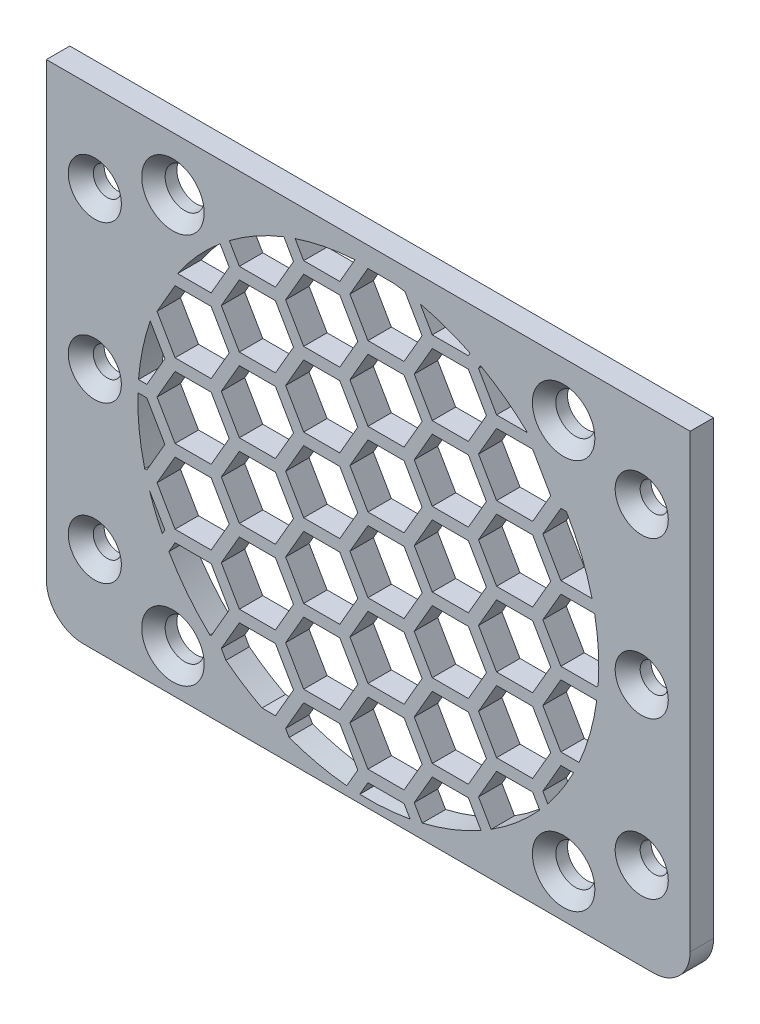
SolidWorks part; units mm, degrees
ref_plane "Front Plane" through (0, 0, 0) normal (0, 0, 1) x (1, 0, 0)
ref_plane "Top Plane" through (0, 0, 0) normal (0, 1, 0) x (1, 0, 0)
ref_plane "Right Plane" through (0, 0, 0) normal (1, 0, 0) x (0, 0, -1)
sketch "Sketch1" plane through (0, 0, 0) normal (0, 0, 1) x (1, 0, 0)
  line L1 (0, 0) -> (11, 0)
  line L2 (0, 0) -> (0, 63)
  line L3 (0, 63) -> (11, 63)
  line L4 (11, 0) -> (11, 63)
  line L5 (0, 0) -> (-61, 0)
  line L6 (0, 0) -> (0, 63)
  line L7 (0, 63) -> (-61, 63)
  line L8 (-61, 0) -> (-61, 63)
  line L9 (-61, 0) -> (-72, 0)
  line L10 (-61, 0) -> (-61, 63)
  line L11 (-61, 63) -> (-72, 63)
  line L12 (-72, 0) -> (-72, 63)
  line L13 (0, 0) -> (-60, 0)
  line L14 (0, 0) -> (0, 60)
  line L15 (0, 60) -> (-60, 60)
  line L16 (-60, 0) -> (-60, 60)
  dimension "D1" = 63
  dimension "D2" = 11
  dimension "D3" = 11
  dimension "D4" = 60
  dimension "D5" = 60
  dimension "D6" = 1
extrude "Boss-Extrude1" add sketch "Sketch1" along normal blind 3 contours L12 L9 L8 L11 | L5 L16 L15 L6 L7 L8 | L16 L5 L2 L15 | L1 L4 L3 L6 L2 region at (5.5, 31.5, 0) region at (-30, 30, 0) region at (-30, 60.8769, 0) region at (-66.5, 31.5, 0)
hole_wizard "CSK for M3 Flat Head Machine Screw1" positions "Sketch2" profile "Sketch3" countersink size "M3" standard "ANSI Metric"
sketch "Sketch2" plane through (0, 0, 3) normal (0, 0, 1) x (1, 0, 0)
  line L0 (-72, 0) -> (-72, 63) construction
  line L1 (11, 0) -> (11, 63) construction
  line L2 (-72, 0) -> (-72, 63) construction
  point P0 (-65.5, 31.5)
  point P2 (-65.5, 51.5)
  point P4 (-65.5, 11.5)
  point P6 (4.5, 11.5)
  point P8 (4.5, 31.5)
  point P10 (4.5, 51.5)
  point P37 (-72, 31.5)
  dimension "D1" = 6.5
  dimension "D2" = 6.5
  dimension "D3" = 20
  dimension "D4" = 20
  dimension "D5" = 20
  dimension "D6" = 20
sketch "Sketch3" plane through (-65.5, 31.5, 3) normal (1, 0, 0) x (0, -1, 0)
  line L0 (0, 0) -> (0, 7.0815)
  line L1 (0, 7.0815) -> (1.8, 6)
  line L2 (1.8, 6) -> (1.8, 1.6)
  line L3 (1.8, 1.6) -> (3.4, 0)
  line L5 (3.4, 0) -> (0, 0)
  line L6 (-1.8, 1.6) -> (-3.4, 0) construction
  line L10 (0, 7.0815) -> (-1.8, 6) construction
  line L11 (0, -6.35) -> (0, 107.95) construction
  dimension "Hole Dia." = 3.6
  dimension "Hole Depth" = 6
  dimension "Near C'Sink Dia." = 6.8
  dimension "Near C'Sink Angle" = 90
  dimension "Drill Angle" = 118
fillet "Fillet1" radius 5 2 edges at (-72, 0, 1.5) (11, 0, 1.5)
sketch "Sketch4" plane through (0, 0, 3) normal (0, 0, 1) x (1, 0, 0)
  line L0 (11, 5) -> (11, 63) construction
  line L1 (6, 0) -> (-67, 0) construction
  line L2 (-72, 5) -> (-72, 63) construction
  line L3 (11, 63) -> (-72, 63) construction
  line L4 (11, 5) -> (11, 63)
  line L5 (6, 0) -> (-67, 0)
  line L6 (-72, 5) -> (-72, 63)
  line L7 (11, 63) -> (-72, 63)
  line L8 (10.7, 5) -> (10.7, 62.7)
  line L9 (10.7, 62.7) -> (-71.7, 62.7)
  line L10 (-71.7, 5) -> (-71.7, 62.7)
  line L11 (6, 0.3) -> (-67, 0.3)
  arc A0 (6, 0) -> (11, 5) centre (6, 5) ccw construction
  arc A1 (-72, 5) -> (-67, 0) centre (-67, 5) ccw construction
  arc A2 (6, 0) -> (11, 5) centre (6, 5) ccw
  arc A3 (-72, 5) -> (-67, 0) centre (-67, 5) ccw
  arc A4 (-71.7, 5) -> (-67, 0.3) centre (-67, 5) ccw
  arc A5 (6, 0.3) -> (10.7, 5) centre (6, 5) ccw
  dimension "D1" = 0.3
extrude "Cut-Extrude1" cut sketch "Sketch4" against normal through all
sketch "Sketch5" plane through (0, 0, 3) normal (0, 0, 1) x (1, 0, 0)
  line L0 (-67, 0.3) -> (6, 0.3) construction
  line L1 (-60.5, 60.8) -> (-0.5, 60.8)
  line L2 (-60.5, 60.8) -> (-60.5, 0.8)
  line L3 (-60.5, 0.8) -> (-0.5, 0.8)
  line L4 (-0.5, 60.8) -> (-0.5, 0.8)
  line L5 (-60.5, 60.8) -> (-0.5, 0.8) construction
  line L6 (-60.5, 0.8) -> (-0.5, 60.8) construction
  line L7 (-55.5, 55.8) -> (-5.5, 55.8)
  line L8 (-55.5, 55.8) -> (-55.5, 5.8)
  line L9 (-55.5, 5.8) -> (-5.5, 5.8)
  line L10 (-5.5, 55.8) -> (-5.5, 5.8)
  line L11 (-55.5, 55.8) -> (-5.5, 5.8) construction
  line L12 (-55.5, 5.8) -> (-5.5, 55.8) construction
  point P0 (-30.5, 30.8)
  point P5 (-30.5, 30.8)
  point P16 (-30.5, 0.3)
  dimension "D1" = 50
  dimension "D2" = 60
  dimension "D3" = 0.5
sketch "Sketch6" plane through (0, 0, 3) normal (0, 0, 1) x (1, 0, 0)
  point P0 (-55.5, 55.8)
  point P3 (-5.5, 55.8)
  point P6 (-5.5, 5.8)
  point P9 (-55.5, 5.8)
hole_wizard "CSK for M4 Flat Head Machine Screw1" positions "Sketch6" profile "Sketch7" countersink size "M4" standard "ANSI Metric"
sketch "Sketch7" plane through (-55.5, 55.8, 3) normal (1, 0, 0) x (0, -1, 0)
  line L0 (0, 0) -> (0, 8.5022)
  line L1 (0, 8.5022) -> (2.5, 7)
  line L2 (2.5, 7) -> (2.5, 1.5)
  line L3 (2.5, 1.5) -> (4, 0)
  line L5 (4, 0) -> (0, 0)
  line L6 (-2.5, 1.5) -> (-4, 0) construction
  line L10 (0, 8.5022) -> (-2.5, 7) construction
  line L11 (0, -6.35) -> (0, 107.95) construction
  dimension "Hole Dia." = 5
  dimension "Hole Depth" = 7
  dimension "Near C'Sink Dia." = 8
  dimension "Near C'Sink Angle" = 90
  dimension "Drill Angle" = 118
sketch "Sketch8" plane through (0, 0, 3) normal (0, 0, 1) x (1, 0, 0)
  circle A0 centre (-30.5, 30.8) radius 29.5
  dimension "D1" = 59
extrude "Cut-Extrude2" cut sketch "Sketch8" against normal through all
sketch "Sketch9" plane through (0, 0, 3) normal (0, 0, 1) x (1, 0, 0)
  line L0 (-36.46, 32.375) -> (-28.2328, 37.125) construction
  line L1 (-31.8412, 32.375) -> (-34.1506, 36.375)
  line L2 (-34.1506, 36.375) -> (-38.7694, 36.375)
  line L3 (-38.7694, 36.375) -> (-41.0788, 32.375)
  line L4 (-41.0788, 32.375) -> (-38.7694, 28.375)
  line L5 (-38.7694, 28.375) -> (-34.1506, 28.375)
  line L6 (-34.1506, 28.375) -> (-31.8412, 32.375)
  line L7 (-23.614, 37.125) -> (-25.9234, 41.125)
  line L8 (-25.9234, 41.125) -> (-30.5422, 41.125)
  line L9 (-30.5422, 41.125) -> (-32.8516, 37.125)
  line L10 (-32.8516, 37.125) -> (-30.5422, 33.125)
  line L11 (-30.5422, 33.125) -> (-25.9234, 33.125)
  line L12 (-25.9234, 33.125) -> (-23.614, 37.125)
  line L13 (-36.46, 32.375) -> (-28.2328, 32.375) construction
  line L14 (-31.8412, 22.875) -> (-34.1506, 26.875)
  line L15 (-34.1506, 26.875) -> (-38.7694, 26.875)
  line L16 (-38.7694, 26.875) -> (-41.0788, 22.875)
  line L17 (-41.0788, 22.875) -> (-38.7694, 18.875)
  line L18 (-38.7694, 18.875) -> (-34.1506, 18.875)
  line L19 (-34.1506, 18.875) -> (-31.8412, 22.875)
  line L20 (-23.614, 27.625) -> (-25.9234, 31.625)
  line L21 (-25.9234, 31.625) -> (-30.5422, 31.625)
  line L22 (-30.5422, 31.625) -> (-32.8516, 27.625)
  line L23 (-32.8516, 27.625) -> (-30.5422, 23.625)
  line L24 (-30.5422, 23.625) -> (-25.9234, 23.625)
  line L25 (-25.9234, 23.625) -> (-23.614, 27.625)
  line L26 (-15.3812, 32.375) -> (-17.6906, 36.375)
  line L27 (-17.6906, 36.375) -> (-22.3094, 36.375)
  line L28 (-22.3094, 36.375) -> (-24.6188, 32.375)
  line L29 (-24.6188, 32.375) -> (-22.3094, 28.375)
  line L30 (-22.3094, 28.375) -> (-17.6906, 28.375)
  line L31 (-17.6906, 28.375) -> (-15.3812, 32.375)
  line L32 (1.0788, 32.375) -> (-1.2306, 36.375)
  line L33 (-1.2306, 36.375) -> (-5.8494, 36.375)
  line L34 (-5.8494, 36.375) -> (-8.1588, 32.375)
  line L35 (-8.1588, 32.375) -> (-5.8494, 28.375)
  line L36 (-5.8494, 28.375) -> (-1.2306, 28.375)
  line L37 (-1.2306, 28.375) -> (1.0788, 32.375)
  line L38 (-15.3812, 22.875) -> (-17.6906, 26.875)
  line L39 (-17.6906, 26.875) -> (-22.3094, 26.875)
  line L40 (-22.3094, 26.875) -> (-24.6188, 22.875)
  line L41 (-24.6188, 22.875) -> (-22.3094, 18.875)
  line L42 (-22.3094, 18.875) -> (-17.6906, 18.875)
  line L43 (-17.6906, 18.875) -> (-15.3812, 22.875)
  line L44 (1.0788, 22.875) -> (-1.2306, 26.875)
  line L45 (-1.2306, 26.875) -> (-5.8494, 26.875)
  line L46 (-5.8494, 26.875) -> (-8.1588, 22.875)
  line L47 (-8.1588, 22.875) -> (-5.8494, 18.875)
  line L48 (-5.8494, 18.875) -> (-1.2306, 18.875)
  line L49 (-1.2306, 18.875) -> (1.0788, 22.875)
  line L50 (-15.3812, 13.375) -> (-17.6906, 17.375)
  line L51 (-17.6906, 17.375) -> (-22.3094, 17.375)
  line L52 (-22.3094, 17.375) -> (-24.6188, 13.375)
  line L53 (-24.6188, 13.375) -> (-22.3094, 9.375)
  line L54 (-22.3094, 9.375) -> (-17.6906, 9.375)
  line L55 (-17.6906, 9.375) -> (-15.3812, 13.375)
  line L56 (1.0788, 13.375) -> (-1.2306, 17.375)
  line L57 (-1.2306, 17.375) -> (-5.8494, 17.375)
  line L58 (-5.8494, 17.375) -> (-8.1588, 13.375)
  line L59 (-8.1588, 13.375) -> (-5.8494, 9.375)
  line L60 (-5.8494, 9.375) -> (-1.2306, 9.375)
  line L61 (-1.2306, 9.375) -> (1.0788, 13.375)
  line L62 (-15.3812, 3.875) -> (-17.6906, 7.875)
  line L63 (-17.6906, 7.875) -> (-22.3094, 7.875)
  line L64 (-22.3094, 7.875) -> (-24.6188, 3.875)
  line L65 (-24.6188, 3.875) -> (-22.3094, -0.125)
  line L66 (-22.3094, -0.125) -> (-17.6906, -0.125)
  line L67 (-17.6906, -0.125) -> (-15.3812, 3.875)
  line L68 (1.0788, 3.875) -> (-1.2306, 7.875)
  line L69 (-1.2306, 7.875) -> (-5.8494, 7.875)
  line L70 (-5.8494, 7.875) -> (-8.1588, 3.875)
  line L71 (-8.1588, 3.875) -> (-5.8494, -0.125)
  line L72 (-5.8494, -0.125) -> (-1.2306, -0.125)
  line L73 (-1.2306, -0.125) -> (1.0788, 3.875)
  line L74 (-31.8412, 22.875) -> (-34.1506, 26.875)
  line L75 (-34.1506, 26.875) -> (-38.7694, 26.875)
  line L76 (-38.7694, 26.875) -> (-41.0788, 22.875)
  line L77 (-41.0788, 22.875) -> (-38.7694, 18.875)
  line L78 (-38.7694, 18.875) -> (-34.1506, 18.875)
  line L79 (-34.1506, 18.875) -> (-31.8412, 22.875)
  line L80 (-31.8412, 13.375) -> (-34.1506, 17.375)
  line L81 (-34.1506, 17.375) -> (-38.7694, 17.375)
  line L82 (-38.7694, 17.375) -> (-41.0788, 13.375)
  line L83 (-41.0788, 13.375) -> (-38.7694, 9.375)
  line L84 (-38.7694, 9.375) -> (-34.1506, 9.375)
  line L85 (-34.1506, 9.375) -> (-31.8412, 13.375)
  line L86 (-31.8412, 3.875) -> (-34.1506, 7.875)
  line L87 (-34.1506, 7.875) -> (-38.7694, 7.875)
  line L88 (-38.7694, 7.875) -> (-41.0788, 3.875)
  line L89 (-41.0788, 3.875) -> (-38.7694, -0.125)
  line L90 (-38.7694, -0.125) -> (-34.1506, -0.125)
  line L91 (-34.1506, -0.125) -> (-31.8412, 3.875)
  line L92 (-31.8412, 41.875) -> (-34.1506, 45.875)
  line L93 (-34.1506, 45.875) -> (-38.7694, 45.875)
  line L94 (-38.7694, 45.875) -> (-41.0788, 41.875)
  line L95 (-41.0788, 41.875) -> (-38.7694, 37.875)
  line L96 (-38.7694, 37.875) -> (-34.1506, 37.875)
  line L97 (-34.1506, 37.875) -> (-31.8412, 41.875)
  line L98 (-15.3812, 41.875) -> (-17.6906, 45.875)
  line L99 (-17.6906, 45.875) -> (-22.3094, 45.875)
  line L100 (-22.3094, 45.875) -> (-24.6188, 41.875)
  line L101 (-24.6188, 41.875) -> (-22.3094, 37.875)
  line L102 (-22.3094, 37.875) -> (-17.6906, 37.875)
  line L103 (-17.6906, 37.875) -> (-15.3812, 41.875)
  line L104 (1.0788, 41.875) -> (-1.2306, 45.875)
  line L105 (-1.2306, 45.875) -> (-5.8494, 45.875)
  line L106 (-5.8494, 45.875) -> (-8.1588, 41.875)
  line L107 (-8.1588, 41.875) -> (-5.8494, 37.875)
  line L108 (-5.8494, 37.875) -> (-1.2306, 37.875)
  line L109 (-1.2306, 37.875) -> (1.0788, 41.875)
  line L110 (-31.8412, 51.375) -> (-34.1506, 55.375)
  line L111 (-34.1506, 55.375) -> (-38.7694, 55.375)
  line L112 (-38.7694, 55.375) -> (-41.0788, 51.375)
  line L113 (-41.0788, 51.375) -> (-38.7694, 47.375)
  line L114 (-38.7694, 47.375) -> (-34.1506, 47.375)
  line L115 (-34.1506, 47.375) -> (-31.8412, 51.375)
  line L116 (-15.3812, 51.375) -> (-17.6906, 55.375)
  line L117 (-17.6906, 55.375) -> (-22.3094, 55.375)
  line L118 (-22.3094, 55.375) -> (-24.6188, 51.375)
  line L119 (-24.6188, 51.375) -> (-22.3094, 47.375)
  line L120 (-22.3094, 47.375) -> (-17.6906, 47.375)
  line L121 (-17.6906, 47.375) -> (-15.3812, 51.375)
  line L122 (1.0788, 51.375) -> (-1.2306, 55.375)
  line L123 (-1.2306, 55.375) -> (-5.8494, 55.375)
  line L124 (-5.8494, 55.375) -> (-8.1588, 51.375)
  line L125 (-8.1588, 51.375) -> (-5.8494, 47.375)
  line L126 (-5.8494, 47.375) -> (-1.2306, 47.375)
  line L127 (-1.2306, 47.375) -> (1.0788, 51.375)
  line L128 (-31.8412, 60.875) -> (-34.1506, 64.875)
  line L129 (-34.1506, 64.875) -> (-38.7694, 64.875)
  line L130 (-38.7694, 64.875) -> (-41.0788, 60.875)
  line L131 (-41.0788, 60.875) -> (-38.7694, 56.875)
  line L132 (-38.7694, 56.875) -> (-34.1506, 56.875)
  line L133 (-34.1506, 56.875) -> (-31.8412, 60.875)
  line L134 (-15.3812, 60.875) -> (-17.6906, 64.875)
  line L135 (-17.6906, 64.875) -> (-22.3094, 64.875)
  line L136 (-22.3094, 64.875) -> (-24.6188, 60.875)
  line L137 (-24.6188, 60.875) -> (-22.3094, 56.875)
  line L138 (-22.3094, 56.875) -> (-17.6906, 56.875)
  line L139 (-17.6906, 56.875) -> (-15.3812, 60.875)
  line L140 (1.0788, 60.875) -> (-1.2306, 64.875)
  line L141 (-1.2306, 64.875) -> (-5.8494, 64.875)
  line L142 (-5.8494, 64.875) -> (-8.1588, 60.875)
  line L143 (-8.1588, 60.875) -> (-5.8494, 56.875)
  line L144 (-5.8494, 56.875) -> (-1.2306, 56.875)
  line L145 (-1.2306, 56.875) -> (1.0788, 60.875)
  line L146 (-23.614, 46.625) -> (-25.9234, 50.625)
  line L147 (-25.9234, 50.625) -> (-30.5422, 50.625)
  line L148 (-30.5422, 50.625) -> (-32.8516, 46.625)
  line L149 (-32.8516, 46.625) -> (-30.5422, 42.625)
  line L150 (-30.5422, 42.625) -> (-25.9234, 42.625)
  line L151 (-25.9234, 42.625) -> (-23.614, 46.625)
  line L152 (-23.614, 56.125) -> (-25.9234, 60.125)
  line L153 (-25.9234, 60.125) -> (-30.5422, 60.125)
  line L154 (-30.5422, 60.125) -> (-32.8516, 56.125)
  line L155 (-32.8516, 56.125) -> (-30.5422, 52.125)
  line L156 (-30.5422, 52.125) -> (-25.9234, 52.125)
  line L157 (-25.9234, 52.125) -> (-23.614, 56.125)
  line L158 (-23.614, 18.125) -> (-25.9234, 22.125)
  line L159 (-25.9234, 22.125) -> (-30.5422, 22.125)
  line L160 (-30.5422, 22.125) -> (-32.8516, 18.125)
  line L161 (-32.8516, 18.125) -> (-30.5422, 14.125)
  line L162 (-30.5422, 14.125) -> (-25.9234, 14.125)
  line L163 (-25.9234, 14.125) -> (-23.614, 18.125)
  line L164 (-23.614, 8.625) -> (-25.9234, 12.625)
  line L165 (-25.9234, 12.625) -> (-30.5422, 12.625)
  line L166 (-30.5422, 12.625) -> (-32.8516, 8.625)
  line L167 (-32.8516, 8.625) -> (-30.5422, 4.625)
  line L168 (-30.5422, 4.625) -> (-25.9234, 4.625)
  line L169 (-25.9234, 4.625) -> (-23.614, 8.625)
  line L170 (-23.614, -0.875) -> (-25.9234, 3.125)
  line L171 (-25.9234, 3.125) -> (-30.5422, 3.125)
  line L172 (-30.5422, 3.125) -> (-32.8516, -0.875)
  line L173 (-32.8516, -0.875) -> (-30.5422, -4.875)
  line L174 (-30.5422, -4.875) -> (-25.9234, -4.875)
  line L175 (-25.9234, -4.875) -> (-23.614, -0.875)
  line L176 (-7.154, 56.125) -> (-9.4634, 60.125)
  line L177 (-9.4634, 60.125) -> (-14.0822, 60.125)
  line L178 (-14.0822, 60.125) -> (-16.3916, 56.125)
  line L179 (-16.3916, 56.125) -> (-14.0822, 52.125)
  line L180 (-14.0822, 52.125) -> (-9.4634, 52.125)
  line L181 (-9.4634, 52.125) -> (-7.154, 56.125)
  line L182 (-7.154, 46.625) -> (-9.4634, 50.625)
  line L183 (-9.4634, 50.625) -> (-14.0822, 50.625)
  line L184 (-14.0822, 50.625) -> (-16.3916, 46.625)
  line L185 (-16.3916, 46.625) -> (-14.0822, 42.625)
  line L186 (-14.0822, 42.625) -> (-9.4634, 42.625)
  line L187 (-9.4634, 42.625) -> (-7.154, 46.625)
  line L188 (-7.154, 37.125) -> (-9.4634, 41.125)
  line L189 (-9.4634, 41.125) -> (-14.0822, 41.125)
  line L190 (-14.0822, 41.125) -> (-16.3916, 37.125)
  line L191 (-16.3916, 37.125) -> (-14.0822, 33.125)
  line L192 (-14.0822, 33.125) -> (-9.4634, 33.125)
  line L193 (-9.4634, 33.125) -> (-7.154, 37.125)
  line L194 (-7.154, 27.625) -> (-9.4634, 31.625)
  line L195 (-9.4634, 31.625) -> (-14.0822, 31.625)
  line L196 (-14.0822, 31.625) -> (-16.3916, 27.625)
  line L197 (-16.3916, 27.625) -> (-14.0822, 23.625)
  line L198 (-14.0822, 23.625) -> (-9.4634, 23.625)
  line L199 (-9.4634, 23.625) -> (-7.154, 27.625)
  line L200 (-7.154, 18.125) -> (-9.4634, 22.125)
  line L201 (-9.4634, 22.125) -> (-14.0822, 22.125)
  line L202 (-14.0822, 22.125) -> (-16.3916, 18.125)
  line L203 (-16.3916, 18.125) -> (-14.0822, 14.125)
  line L204 (-14.0822, 14.125) -> (-9.4634, 14.125)
  line L205 (-9.4634, 14.125) -> (-7.154, 18.125)
  line L206 (-7.154, 8.625) -> (-9.4634, 12.625)
  line L207 (-9.4634, 12.625) -> (-14.0822, 12.625)
  line L208 (-14.0822, 12.625) -> (-16.3916, 8.625)
  line L209 (-16.3916, 8.625) -> (-14.0822, 4.625)
  line L210 (-14.0822, 4.625) -> (-9.4634, 4.625)
  line L211 (-9.4634, 4.625) -> (-7.154, 8.625)
  line L212 (-48.3012, 60.875) -> (-50.6106, 64.875)
  line L213 (-50.6106, 64.875) -> (-55.2294, 64.875)
  line L214 (-55.2294, 64.875) -> (-57.5388, 60.875)
  line L215 (-57.5388, 60.875) -> (-55.2294, 56.875)
  line L216 (-55.2294, 56.875) -> (-50.6106, 56.875)
  line L217 (-50.6106, 56.875) -> (-48.3012, 60.875)
  line L218 (-48.3012, 51.375) -> (-50.6106, 55.375)
  line L219 (-50.6106, 55.375) -> (-55.2294, 55.375)
  line L220 (-55.2294, 55.375) -> (-57.5388, 51.375)
  line L221 (-57.5388, 51.375) -> (-55.2294, 47.375)
  line L222 (-55.2294, 47.375) -> (-50.6106, 47.375)
  line L223 (-50.6106, 47.375) -> (-48.3012, 51.375)
  line L224 (-40.074, 56.125) -> (-42.3834, 60.125)
  line L225 (-42.3834, 60.125) -> (-47.0022, 60.125)
  line L226 (-47.0022, 60.125) -> (-49.3116, 56.125)
  line L227 (-49.3116, 56.125) -> (-47.0022, 52.125)
  line L228 (-47.0022, 52.125) -> (-42.3834, 52.125)
  line L229 (-42.3834, 52.125) -> (-40.074, 56.125)
  line L230 (-40.074, 46.625) -> (-42.3834, 50.625)
  line L231 (-42.3834, 50.625) -> (-47.0022, 50.625)
  line L232 (-47.0022, 50.625) -> (-49.3116, 46.625)
  line L233 (-49.3116, 46.625) -> (-47.0022, 42.625)
  line L234 (-47.0022, 42.625) -> (-42.3834, 42.625)
  line L235 (-42.3834, 42.625) -> (-40.074, 46.625)
  line L236 (-48.3012, 41.875) -> (-50.6106, 45.875)
  line L237 (-50.6106, 45.875) -> (-55.2294, 45.875)
  line L238 (-55.2294, 45.875) -> (-57.5388, 41.875)
  line L239 (-57.5388, 41.875) -> (-55.2294, 37.875)
  line L240 (-55.2294, 37.875) -> (-50.6106, 37.875)
  line L241 (-50.6106, 37.875) -> (-48.3012, 41.875)
  line L242 (-40.074, 37.125) -> (-42.3834, 41.125)
  line L243 (-42.3834, 41.125) -> (-47.0022, 41.125)
  line L244 (-47.0022, 41.125) -> (-49.3116, 37.125)
  line L245 (-49.3116, 37.125) -> (-47.0022, 33.125)
  line L246 (-47.0022, 33.125) -> (-42.3834, 33.125)
  line L247 (-42.3834, 33.125) -> (-40.074, 37.125)
  line L248 (-48.3012, 32.375) -> (-50.6106, 36.375)
  line L249 (-50.6106, 36.375) -> (-55.2294, 36.375)
  line L250 (-55.2294, 36.375) -> (-57.5388, 32.375)
  line L251 (-57.5388, 32.375) -> (-55.2294, 28.375)
  line L252 (-55.2294, 28.375) -> (-50.6106, 28.375)
  line L253 (-50.6106, 28.375) -> (-48.3012, 32.375)
  line L254 (-40.074, 27.625) -> (-42.3834, 31.625)
  line L255 (-42.3834, 31.625) -> (-47.0022, 31.625)
  line L256 (-47.0022, 31.625) -> (-49.3116, 27.625)
  line L257 (-49.3116, 27.625) -> (-47.0022, 23.625)
  line L258 (-47.0022, 23.625) -> (-42.3834, 23.625)
  line L259 (-42.3834, 23.625) -> (-40.074, 27.625)
  line L260 (-48.3012, 22.875) -> (-50.6106, 26.875)
  line L261 (-50.6106, 26.875) -> (-55.2294, 26.875)
  line L262 (-55.2294, 26.875) -> (-57.5388, 22.875)
  line L263 (-57.5388, 22.875) -> (-55.2294, 18.875)
  line L264 (-55.2294, 18.875) -> (-50.6106, 18.875)
  line L265 (-50.6106, 18.875) -> (-48.3012, 22.875)
  line L266 (-40.074, 18.125) -> (-42.3834, 22.125)
  line L267 (-42.3834, 22.125) -> (-47.0022, 22.125)
  line L268 (-47.0022, 22.125) -> (-49.3116, 18.125)
  line L269 (-49.3116, 18.125) -> (-47.0022, 14.125)
  line L270 (-47.0022, 14.125) -> (-42.3834, 14.125)
  line L271 (-42.3834, 14.125) -> (-40.074, 18.125)
  line L272 (-48.3012, 13.375) -> (-50.6106, 17.375)
  line L273 (-50.6106, 17.375) -> (-55.2294, 17.375)
  line L274 (-55.2294, 17.375) -> (-57.5388, 13.375)
  line L275 (-57.5388, 13.375) -> (-55.2294, 9.375)
  line L276 (-55.2294, 9.375) -> (-50.6106, 9.375)
  line L277 (-50.6106, 9.375) -> (-48.3012, 13.375)
  line L278 (-40.074, 8.625) -> (-42.3834, 12.625)
  line L279 (-42.3834, 12.625) -> (-47.0022, 12.625)
  line L280 (-47.0022, 12.625) -> (-49.3116, 8.625)
  line L281 (-49.3116, 8.625) -> (-47.0022, 4.625)
  line L282 (-47.0022, 4.625) -> (-42.3834, 4.625)
  line L283 (-42.3834, 4.625) -> (-40.074, 8.625)
  line L284 (-48.3012, 3.875) -> (-50.6106, 7.875)
  line L285 (-50.6106, 7.875) -> (-55.2294, 7.875)
  line L286 (-55.2294, 7.875) -> (-57.5388, 3.875)
  line L287 (-57.5388, 3.875) -> (-55.2294, -0.125)
  line L288 (-55.2294, -0.125) -> (-50.6106, -0.125)
  line L289 (-50.6106, -0.125) -> (-48.3012, 3.875)
  line L290 (-40.074, -0.875) -> (-42.3834, 3.125)
  line L291 (-42.3834, 3.125) -> (-47.0022, 3.125)
  line L292 (-47.0022, 3.125) -> (-49.3116, -0.875)
  line L293 (-49.3116, -0.875) -> (-47.0022, -4.875)
  line L294 (-47.0022, -4.875) -> (-42.3834, -4.875)
  line L295 (-42.3834, -4.875) -> (-40.074, -0.875)
  line L296 (-64.7612, 60.875) -> (-67.0706, 64.875)
  line L297 (-67.0706, 64.875) -> (-71.6894, 64.875)
  line L298 (-71.6894, 64.875) -> (-73.9988, 60.875)
  line L299 (-73.9988, 60.875) -> (-71.6894, 56.875)
  line L300 (-71.6894, 56.875) -> (-67.0706, 56.875)
  line L301 (-67.0706, 56.875) -> (-64.7612, 60.875)
  line L302 (-64.7612, 51.375) -> (-67.0706, 55.375)
  line L303 (-67.0706, 55.375) -> (-71.6894, 55.375)
  line L304 (-71.6894, 55.375) -> (-73.9988, 51.375)
  line L305 (-73.9988, 51.375) -> (-71.6894, 47.375)
  line L306 (-71.6894, 47.375) -> (-67.0706, 47.375)
  line L307 (-67.0706, 47.375) -> (-64.7612, 51.375)
  line L308 (-56.534, 56.125) -> (-58.8434, 60.125)
  line L309 (-58.8434, 60.125) -> (-63.4622, 60.125)
  line L310 (-63.4622, 60.125) -> (-65.7716, 56.125)
  line L311 (-65.7716, 56.125) -> (-63.4622, 52.125)
  line L312 (-63.4622, 52.125) -> (-58.8434, 52.125)
  line L313 (-58.8434, 52.125) -> (-56.534, 56.125)
  line L314 (-56.534, 46.625) -> (-58.8434, 50.625)
  line L315 (-58.8434, 50.625) -> (-63.4622, 50.625)
  line L316 (-63.4622, 50.625) -> (-65.7716, 46.625)
  line L317 (-65.7716, 46.625) -> (-63.4622, 42.625)
  line L318 (-63.4622, 42.625) -> (-58.8434, 42.625)
  line L319 (-58.8434, 42.625) -> (-56.534, 46.625)
  line L320 (-64.7612, 41.875) -> (-67.0706, 45.875)
  line L321 (-67.0706, 45.875) -> (-71.6894, 45.875)
  line L322 (-71.6894, 45.875) -> (-73.9988, 41.875)
  line L323 (-73.9988, 41.875) -> (-71.6894, 37.875)
  line L324 (-71.6894, 37.875) -> (-67.0706, 37.875)
  line L325 (-67.0706, 37.875) -> (-64.7612, 41.875)
  line L326 (-56.534, 37.125) -> (-58.8434, 41.125)
  line L327 (-58.8434, 41.125) -> (-63.4622, 41.125)
  line L328 (-63.4622, 41.125) -> (-65.7716, 37.125)
  line L329 (-65.7716, 37.125) -> (-63.4622, 33.125)
  line L330 (-63.4622, 33.125) -> (-58.8434, 33.125)
  line L331 (-58.8434, 33.125) -> (-56.534, 37.125)
  line L332 (-64.7612, 32.375) -> (-67.0706, 36.375)
  line L333 (-67.0706, 36.375) -> (-71.6894, 36.375)
  line L334 (-71.6894, 36.375) -> (-73.9988, 32.375)
  line L335 (-73.9988, 32.375) -> (-71.6894, 28.375)
  line L336 (-71.6894, 28.375) -> (-67.0706, 28.375)
  line L337 (-67.0706, 28.375) -> (-64.7612, 32.375)
  line L338 (-56.534, 27.625) -> (-58.8434, 31.625)
  line L339 (-58.8434, 31.625) -> (-63.4622, 31.625)
  line L340 (-63.4622, 31.625) -> (-65.7716, 27.625)
  line L341 (-65.7716, 27.625) -> (-63.4622, 23.625)
  line L342 (-63.4622, 23.625) -> (-58.8434, 23.625)
  line L343 (-58.8434, 23.625) -> (-56.534, 27.625)
  line L344 (-64.7612, 22.875) -> (-67.0706, 26.875)
  line L345 (-67.0706, 26.875) -> (-71.6894, 26.875)
  line L346 (-71.6894, 26.875) -> (-73.9988, 22.875)
  line L347 (-73.9988, 22.875) -> (-71.6894, 18.875)
  line L348 (-71.6894, 18.875) -> (-67.0706, 18.875)
  line L349 (-67.0706, 18.875) -> (-64.7612, 22.875)
  line L350 (-56.534, 18.125) -> (-58.8434, 22.125)
  line L351 (-58.8434, 22.125) -> (-63.4622, 22.125)
  line L352 (-63.4622, 22.125) -> (-65.7716, 18.125)
  line L353 (-65.7716, 18.125) -> (-63.4622, 14.125)
  line L354 (-63.4622, 14.125) -> (-58.8434, 14.125)
  line L355 (-58.8434, 14.125) -> (-56.534, 18.125)
  line L356 (-64.7612, 13.375) -> (-67.0706, 17.375)
  line L357 (-67.0706, 17.375) -> (-71.6894, 17.375)
  line L358 (-71.6894, 17.375) -> (-73.9988, 13.375)
  line L359 (-73.9988, 13.375) -> (-71.6894, 9.375)
  line L360 (-71.6894, 9.375) -> (-67.0706, 9.375)
  line L361 (-67.0706, 9.375) -> (-64.7612, 13.375)
  line L362 (-56.534, 8.625) -> (-58.8434, 12.625)
  line L363 (-58.8434, 12.625) -> (-63.4622, 12.625)
  line L364 (-63.4622, 12.625) -> (-65.7716, 8.625)
  line L365 (-65.7716, 8.625) -> (-63.4622, 4.625)
  line L366 (-63.4622, 4.625) -> (-58.8434, 4.625)
  line L367 (-58.8434, 4.625) -> (-56.534, 8.625)
  line L368 (-64.7612, 3.875) -> (-67.0706, 7.875)
  line L369 (-67.0706, 7.875) -> (-71.6894, 7.875)
  line L370 (-71.6894, 7.875) -> (-73.9988, 3.875)
  line L371 (-73.9988, 3.875) -> (-71.6894, -0.125)
  line L372 (-71.6894, -0.125) -> (-67.0706, -0.125)
  line L373 (-67.0706, -0.125) -> (-64.7612, 3.875)
  line L374 (-56.534, -0.875) -> (-58.8434, 3.125)
  line L375 (-58.8434, 3.125) -> (-63.4622, 3.125)
  line L376 (-63.4622, 3.125) -> (-65.7716, -0.875)
  line L377 (-65.7716, -0.875) -> (-63.4622, -4.875)
  line L378 (-63.4622, -4.875) -> (-58.8434, -4.875)
  line L379 (-58.8434, -4.875) -> (-56.534, -0.875)
  line L380 (9.306, 56.125) -> (6.9966, 60.125)
  line L381 (6.9966, 60.125) -> (2.3778, 60.125)
  line L382 (2.3778, 60.125) -> (0.0684, 56.125)
  line L383 (0.0684, 56.125) -> (2.3778, 52.125)
  line L384 (2.3778, 52.125) -> (6.9966, 52.125)
  line L385 (6.9966, 52.125) -> (9.306, 56.125)
  line L386 (17.5388, 60.875) -> (15.2294, 64.875)
  line L387 (15.2294, 64.875) -> (10.6106, 64.875)
  line L388 (10.6106, 64.875) -> (8.3012, 60.875)
  line L389 (8.3012, 60.875) -> (10.6106, 56.875)
  line L390 (10.6106, 56.875) -> (15.2294, 56.875)
  line L391 (15.2294, 56.875) -> (17.5388, 60.875)
  line L392 (17.5388, 51.375) -> (15.2294, 55.375)
  line L393 (15.2294, 55.375) -> (10.6106, 55.375)
  line L394 (10.6106, 55.375) -> (8.3012, 51.375)
  line L395 (8.3012, 51.375) -> (10.6106, 47.375)
  line L396 (10.6106, 47.375) -> (15.2294, 47.375)
  line L397 (15.2294, 47.375) -> (17.5388, 51.375)
  line L398 (9.306, 46.625) -> (6.9966, 50.625)
  line L399 (6.9966, 50.625) -> (2.3778, 50.625)
  line L400 (2.3778, 50.625) -> (0.0684, 46.625)
  line L401 (0.0684, 46.625) -> (2.3778, 42.625)
  line L402 (2.3778, 42.625) -> (6.9966, 42.625)
  line L403 (6.9966, 42.625) -> (9.306, 46.625)
  line L404 (17.5388, 41.875) -> (15.2294, 45.875)
  line L405 (15.2294, 45.875) -> (10.6106, 45.875)
  line L406 (10.6106, 45.875) -> (8.3012, 41.875)
  line L407 (8.3012, 41.875) -> (10.6106, 37.875)
  line L408 (10.6106, 37.875) -> (15.2294, 37.875)
  line L409 (15.2294, 37.875) -> (17.5388, 41.875)
  line L410 (9.306, 37.125) -> (6.9966, 41.125)
  line L411 (6.9966, 41.125) -> (2.3778, 41.125)
  line L412 (2.3778, 41.125) -> (0.0684, 37.125)
  line L413 (0.0684, 37.125) -> (2.3778, 33.125)
  line L414 (2.3778, 33.125) -> (6.9966, 33.125)
  line L415 (6.9966, 33.125) -> (9.306, 37.125)
  line L416 (17.5388, 32.375) -> (15.2294, 36.375)
  line L417 (15.2294, 36.375) -> (10.6106, 36.375)
  line L418 (10.6106, 36.375) -> (8.3012, 32.375)
  line L419 (8.3012, 32.375) -> (10.6106, 28.375)
  line L420 (10.6106, 28.375) -> (15.2294, 28.375)
  line L421 (15.2294, 28.375) -> (17.5388, 32.375)
  line L422 (9.306, 27.625) -> (6.9966, 31.625)
  line L423 (6.9966, 31.625) -> (2.3778, 31.625)
  line L424 (2.3778, 31.625) -> (0.0684, 27.625)
  line L425 (0.0684, 27.625) -> (2.3778, 23.625)
  line L426 (2.3778, 23.625) -> (6.9966, 23.625)
  line L427 (6.9966, 23.625) -> (9.306, 27.625)
  line L428 (17.5388, 22.875) -> (15.2294, 26.875)
  line L429 (15.2294, 26.875) -> (10.6106, 26.875)
  line L430 (10.6106, 26.875) -> (8.3012, 22.875)
  line L431 (8.3012, 22.875) -> (10.6106, 18.875)
  line L432 (10.6106, 18.875) -> (15.2294, 18.875)
  line L433 (15.2294, 18.875) -> (17.5388, 22.875)
  line L434 (9.306, 18.125) -> (6.9966, 22.125)
  line L435 (6.9966, 22.125) -> (2.3778, 22.125)
  line L436 (2.3778, 22.125) -> (0.0684, 18.125)
  line L437 (0.0684, 18.125) -> (2.3778, 14.125)
  line L438 (2.3778, 14.125) -> (6.9966, 14.125)
  line L439 (6.9966, 14.125) -> (9.306, 18.125)
  line L440 (17.5388, 13.375) -> (15.2294, 17.375)
  line L441 (15.2294, 17.375) -> (10.6106, 17.375)
  line L442 (10.6106, 17.375) -> (8.3012, 13.375)
  line L443 (8.3012, 13.375) -> (10.6106, 9.375)
  line L444 (10.6106, 9.375) -> (15.2294, 9.375)
  line L445 (15.2294, 9.375) -> (17.5388, 13.375)
  line L446 (9.306, 8.625) -> (6.9966, 12.625)
  line L447 (6.9966, 12.625) -> (2.3778, 12.625)
  line L448 (2.3778, 12.625) -> (0.0684, 8.625)
  line L449 (0.0684, 8.625) -> (2.3778, 4.625)
  line L450 (2.3778, 4.625) -> (6.9966, 4.625)
  line L451 (6.9966, 4.625) -> (9.306, 8.625)
  line L452 (17.5388, 3.875) -> (15.2294, 7.875)
  line L453 (15.2294, 7.875) -> (10.6106, 7.875)
  line L454 (10.6106, 7.875) -> (8.3012, 3.875)
  line L455 (8.3012, 3.875) -> (10.6106, -0.125)
  line L456 (10.6106, -0.125) -> (15.2294, -0.125)
  line L457 (15.2294, -0.125) -> (17.5388, 3.875)
  line L458 (25.766, 56.125) -> (23.4566, 60.125)
  line L459 (23.4566, 60.125) -> (18.8378, 60.125)
  line L460 (18.8378, 60.125) -> (16.5284, 56.125)
  line L461 (16.5284, 56.125) -> (18.8378, 52.125)
  line L462 (18.8378, 52.125) -> (23.4566, 52.125)
  line L463 (23.4566, 52.125) -> (25.766, 56.125)
  line L464 (33.9988, 60.875) -> (31.6894, 64.875)
  line L465 (31.6894, 64.875) -> (27.0706, 64.875)
  line L466 (27.0706, 64.875) -> (24.7612, 60.875)
  line L467 (24.7612, 60.875) -> (27.0706, 56.875)
  line L468 (27.0706, 56.875) -> (31.6894, 56.875)
  line L469 (31.6894, 56.875) -> (33.9988, 60.875)
  line L470 (33.9988, 51.375) -> (31.6894, 55.375)
  line L471 (31.6894, 55.375) -> (27.0706, 55.375)
  line L472 (27.0706, 55.375) -> (24.7612, 51.375)
  line L473 (24.7612, 51.375) -> (27.0706, 47.375)
  line L474 (27.0706, 47.375) -> (31.6894, 47.375)
  line L475 (31.6894, 47.375) -> (33.9988, 51.375)
  line L476 (25.766, 46.625) -> (23.4566, 50.625)
  line L477 (23.4566, 50.625) -> (18.8378, 50.625)
  line L478 (18.8378, 50.625) -> (16.5284, 46.625)
  line L479 (16.5284, 46.625) -> (18.8378, 42.625)
  line L480 (18.8378, 42.625) -> (23.4566, 42.625)
  line L481 (23.4566, 42.625) -> (25.766, 46.625)
  line L482 (33.9988, 41.875) -> (31.6894, 45.875)
  line L483 (31.6894, 45.875) -> (27.0706, 45.875)
  line L484 (27.0706, 45.875) -> (24.7612, 41.875)
  line L485 (24.7612, 41.875) -> (27.0706, 37.875)
  line L486 (27.0706, 37.875) -> (31.6894, 37.875)
  line L487 (31.6894, 37.875) -> (33.9988, 41.875)
  line L488 (25.766, 37.125) -> (23.4566, 41.125)
  line L489 (23.4566, 41.125) -> (18.8378, 41.125)
  line L490 (18.8378, 41.125) -> (16.5284, 37.125)
  line L491 (16.5284, 37.125) -> (18.8378, 33.125)
  line L492 (18.8378, 33.125) -> (23.4566, 33.125)
  line L493 (23.4566, 33.125) -> (25.766, 37.125)
  line L494 (33.9988, 32.375) -> (31.6894, 36.375)
  line L495 (31.6894, 36.375) -> (27.0706, 36.375)
  line L496 (27.0706, 36.375) -> (24.7612, 32.375)
  line L497 (24.7612, 32.375) -> (27.0706, 28.375)
  line L498 (27.0706, 28.375) -> (31.6894, 28.375)
  line L499 (31.6894, 28.375) -> (33.9988, 32.375)
  line L500 (25.766, 27.625) -> (23.4566, 31.625)
  line L501 (23.4566, 31.625) -> (18.8378, 31.625)
  line L502 (18.8378, 31.625) -> (16.5284, 27.625)
  line L503 (16.5284, 27.625) -> (18.8378, 23.625)
  line L504 (18.8378, 23.625) -> (23.4566, 23.625)
  line L505 (23.4566, 23.625) -> (25.766, 27.625)
  line L506 (33.9988, 22.875) -> (31.6894, 26.875)
  line L507 (31.6894, 26.875) -> (27.0706, 26.875)
  line L508 (27.0706, 26.875) -> (24.7612, 22.875)
  line L509 (24.7612, 22.875) -> (27.0706, 18.875)
  line L510 (27.0706, 18.875) -> (31.6894, 18.875)
  line L511 (31.6894, 18.875) -> (33.9988, 22.875)
  line L512 (25.766, 18.125) -> (23.4566, 22.125)
  line L513 (23.4566, 22.125) -> (18.8378, 22.125)
  line L514 (18.8378, 22.125) -> (16.5284, 18.125)
  line L515 (16.5284, 18.125) -> (18.8378, 14.125)
  line L516 (18.8378, 14.125) -> (23.4566, 14.125)
  line L517 (23.4566, 14.125) -> (25.766, 18.125)
  line L518 (33.9988, 13.375) -> (31.6894, 17.375)
  line L519 (31.6894, 17.375) -> (27.0706, 17.375)
  line L520 (27.0706, 17.375) -> (24.7612, 13.375)
  line L521 (24.7612, 13.375) -> (27.0706, 9.375)
  line L522 (27.0706, 9.375) -> (31.6894, 9.375)
  line L523 (31.6894, 9.375) -> (33.9988, 13.375)
  line L524 (25.766, 8.625) -> (23.4566, 12.625)
  line L525 (23.4566, 12.625) -> (18.8378, 12.625)
  line L526 (18.8378, 12.625) -> (16.5284, 8.625)
  line L527 (16.5284, 8.625) -> (18.8378, 4.625)
  line L528 (18.8378, 4.625) -> (23.4566, 4.625)
  line L529 (23.4566, 4.625) -> (25.766, 8.625)
  line L530 (33.9988, 3.875) -> (31.6894, 7.875)
  line L531 (31.6894, 7.875) -> (27.0706, 7.875)
  line L532 (27.0706, 7.875) -> (24.7612, 3.875)
  line L533 (24.7612, 3.875) -> (27.0706, -0.125)
  line L534 (27.0706, -0.125) -> (31.6894, -0.125)
  line L535 (31.6894, -0.125) -> (33.9988, 3.875)
  circle A1 centre (-36.46, 32.375) radius 4 construction
  circle A2 centre (-28.2328, 37.125) radius 4 construction
  circle A3 centre (-30.5, 30.8) radius 29.5 construction
  circle A4 centre (-30.5, 30.8) radius 29.5
  circle M115 centre (-30.5, 30.8) radius 29.5
extrude "Boss-Extrude2" add sketch "Sketch9" against normal through all contours L355 L274 L273 L272 L277 L276 L281 L280 L279 L278 L283 L282 L89 L88 L87 L86 L91 L172 L171 L170 L65 L64 L63 L62 L209 L208 L207 L206 L59 L58 L57 L48 L47 L46 L45 L37 L36 L35 L34 L33 L108 M115 region at (-1.9868, 27.8406, 3)
